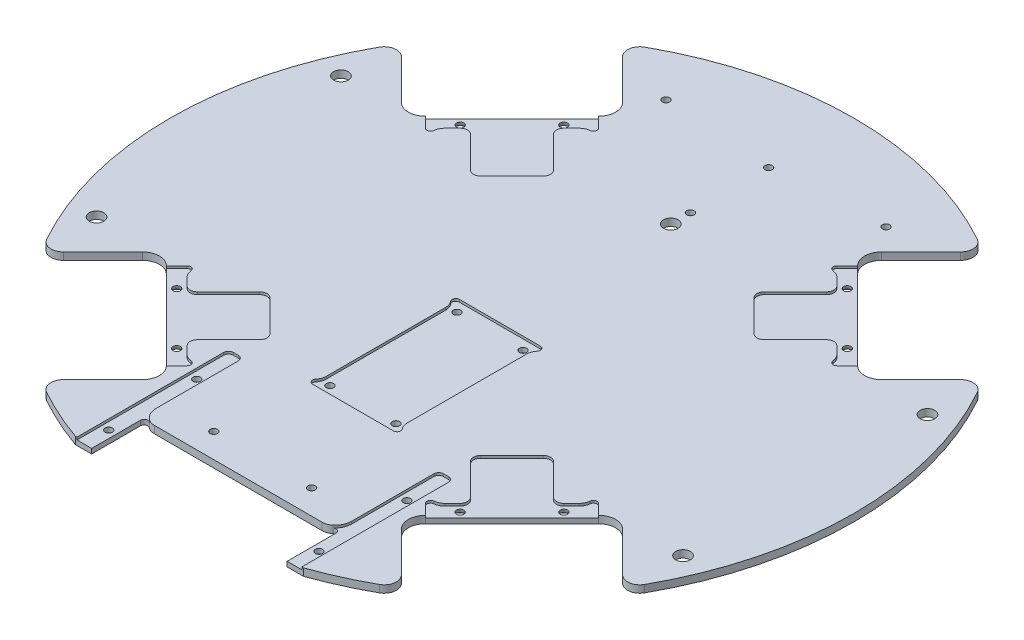
SolidWorks part; units mm, degrees
material "1060 Alloy"
ref_plane "Front Plane" through (0, 0, 0) normal (0, 0, 1) x (1, 0, 0)
ref_plane "Top Plane" through (0, 0, 0) normal (0, 1, 0) x (1, 0, 0)
ref_plane "Right Plane" through (0, 0, 0) normal (1, 0, 0) x (0, 0, -1)
sketch "Sketch1" plane through (0, 0, 0) normal (0, 1, 0) x (1, 0, 0)
  circle A0 centre (0, 0) radius 140
  dimension "D1" = 280
extrude "Boss-Extrude1" add sketch "Sketch1" along normal blind 3
sketch "Sketch7" plane through (0, 3, 0) normal (0, 1, 0) x (1, 0, 0)
  line L0 (-88.4237, -52.9977) -> (-52.9977, -88.4237)
  line L1 (-98.2525, -52.9977) -> (-121.6224, -76.3675)
  line L2 (-52.9977, -98.2525) -> (-76.3675, -121.6224)
  line L3 (-121.6224, -76.3675) -> (-76.3675, -121.6224)
  line L4 (0, 0) -> (-98.9949, -98.9949) construction
  line L7 (0, 0) -> (0, 130) construction
  circle A0 centre (0, 0) radius 140 construction
  arc A1 (-98.2525, -52.9977) -> (-88.4237, -52.9977) centre (-93.3381, -57.912) cw
  arc A2 (-52.9977, -88.4237) -> (-52.9977, -98.2525) centre (-57.912, -93.3381) cw
  dimension "D4" = 6.95
  dimension "D1" = 100
  dimension "D2" = 64
  dimension "D3" = 135
extrude "Cut-Extrude4" cut sketch "Sketch7" against normal up to next
sketch "Sketch8" plane through (0, 3, 0) normal (0, 1, 0) x (1, 0, 0)
  line L0 (-88.4237, -52.9977) -> (-52.9977, -88.4237)
  line L1 (-88.4237, -52.9977) -> (-84.1811, -48.755)
  line L2 (-52.9977, -88.4237) -> (-48.755, -84.1811)
  line L3 (-80.1836, -52.7525) -> (-52.7525, -80.1836)
  line L6 (-52.9977, -88.4237) -> (-88.4237, -52.9977) construction
  arc A0 (-84.1811, -48.755) -> (-81.6268, -49.6775) centre (-83.1204, -49.8157) cw
  arc A1 (-81.6268, -49.6775) -> (-80.1836, -52.7525) centre (-76.648, -49.217) ccw
  arc A2 (-48.755, -84.1811) -> (-49.6775, -81.6268) centre (-49.8157, -83.1204) ccw
  arc A3 (-49.6775, -81.6268) -> (-52.7525, -80.1836) centre (-49.217, -76.648) cw
  dimension "D2" = 1.5
  dimension "D3" = 5
  dimension "D4" = 1.5
  dimension "D5" = 5
  dimension "D1" = 6
extrude "Cut-Extrude5" cut sketch "Sketch8" against normal blind 1
sketch "Sketch14" plane through (0, 3, 0) normal (0, 1, 0) x (1, 0, 0)
  line L0 (-52.7525, -80.1836) -> (-80.1836, -52.7525) construction
  line L1 (-52.7525, -80.1836) -> (-80.1836, -52.7525) construction
  line L2 (-72.832, -55.8614) -> (-60.1041, -43.1335)
  line L3 (-55.8614, -72.832) -> (-43.1335, -60.1041)
  line L4 (-55.8614, -43.1335) -> (-43.1335, -55.8614)
  line L5 (-77.0746, -55.8614) -> (-55.8614, -77.0746)
  line L8 (-84.1811, -48.755) -> (-88.4237, -52.9977) construction
  arc A0 (-77.0746, -55.8614) -> (-72.832, -55.8614) centre (-74.9533, -53.7401) ccw
  arc A1 (-55.8614, -77.0746) -> (-55.8614, -72.832) centre (-53.7401, -74.9533) cw
  arc A2 (-60.1041, -43.1335) -> (-55.8614, -43.1335) centre (-57.9828, -45.2548) cw
  arc A3 (-43.1335, -60.1041) -> (-43.1335, -55.8614) centre (-45.2548, -57.9828) ccw
  dimension "D1" = 3
  dimension "D2" = 24
  dimension "D3" = 24
  dimension "D4" = 13.05
extrude "Cut-Extrude10" cut sketch "Sketch14" against normal up to surface (1 mm away) up to face at (-67.2361, 2, 67.2361)
sketch "Sketch9" plane through (0, 2, 0) normal (0, 1, 0) x (1, 0, 0)
  line L0 (-48.755, -84.1811) -> (-84.1811, -48.755) construction
  line L3 (-48.755, -84.1811) -> (-84.1811, -48.755) construction
  line L4 (-98.2525, -52.9977) -> (-119.0017, -73.7469) construction
  circle A0 centre (-79.196, -57.9828) radius 1.5
  circle A1 centre (-57.9828, -79.196) radius 1.5
  dimension "D4" = 3
  dimension "D1" = 3
  dimension "D2" = 30
  dimension "D3" = 17
  dimension "D5" = 3
extrude "Cut-Extrude6" cut sketch "Sketch9" against normal up to next
fillet "Fillet1" radius 5 2 edges at (-73.7469, 1.5, 119.0017) (-119.0017, 1.5, 73.7469)
pattern_circular "CirPattern1" count 4 over 360 about axis through (0, 3, 0) along (0, 1, 0) of "Cut-Extrude4", "Cut-Extrude6", "Fillet1", "Cut-Extrude5", "Cut-Extrude10"
sketch "Sketch2" plane through (0, 3, 0) normal (0, 1, 0) x (1, 0, 0)
  line L0 (-46.6476, -132) -> (-40, -132)
  line L1 (-40, -132) -> (-40, -112)
  line L2 (-34.3467, -112) -> (34.3467, -112)
  line L3 (40, -112) -> (40, -132)
  line L4 (40, -132) -> (46.6476, -132)
  line L5 (46.6476, -132) -> (46.6476, -140)
  line L6 (46.6476, -140) -> (-46.6476, -140)
  line L7 (-46.6476, -140) -> (-46.6476, -132)
  circle A0 centre (0, 0) radius 140 construction
  arc A1 (-40, -112) -> (-37.5415, -110.8462) centre (-38.5, -112) cw
  arc A2 (-34.3467, -112) -> (-37.5415, -110.8462) centre (-34.3467, -107) cw
  arc A3 (40, -112) -> (37.5415, -110.8462) centre (38.5, -112) ccw
  arc A4 (34.3467, -112) -> (37.5415, -110.8462) centre (34.3467, -107) ccw
  dimension "D5" = 1.5
  dimension "D6" = 5
  dimension "D1" = 8
  dimension "D2" = 20
  dimension "D3" = 80
  dimension "D4" = 6.6476
extrude "Cut-Extrude1" cut sketch "Sketch2" against normal up to next
sketch "Sketch3" plane through (0, 3, 0) normal (0, 1, 0) x (1, 0, 0)
  line L0 (-40, -132) -> (-46.6476, -132) construction
  line L1 (-40, -132) -> (-46, -132)
  line L2 (-40, -132) -> (-40, -72)
  line L3 (-42, -70) -> (-44, -70)
  line L4 (-46, -132) -> (-46, -72)
  line L5 (40, -132) -> (46, -132)
  line L6 (40, -132) -> (40, -72)
  line L7 (42, -70) -> (44, -70)
  line L8 (46, -132) -> (46, -72)
  line L12 (-40, -112) -> (-40, -132) construction
  line L13 (40, -132) -> (40, -112) construction
  arc A0 (40, -72) -> (42, -70) centre (42, -72) cw
  arc A1 (44, -70) -> (46, -72) centre (44, -72) cw
  arc A2 (-40, -72) -> (-42, -70) centre (-42, -72) ccw
  arc A3 (-44, -70) -> (-46, -72) centre (-44, -72) ccw
  dimension "D5" = 2
  dimension "D1" = 6
  dimension "D2" = 62
extrude "Cut-Extrude2" cut sketch "Sketch3" against normal blind 1
sketch "Sketch18" plane through (0, 3, 0) normal (0, 1, 0) x (1, 0, 0)
  line L0 (-40, -112) -> (-40, -72) construction
  line L1 (-40, -112) -> (-40, -72) construction
  line L3 (-40, -105.608) -> (-40, -112)
  line L4 (-40, -112) -> (-37.5415, -110.8462)
  line L5 (40, -72) -> (40, -112) construction
  line L6 (40, -105.608) -> (40, -112)
  line L7 (40, -112) -> (37.5415, -110.8462)
  arc A0 (-37.5415, -110.8462) -> (-40, -105.608) centre (-33.1904, -105.608) cw
  arc A2 (-37.5415, -110.8462) -> (-34.3467, -112) centre (-34.3467, -107) ccw construction
  arc A3 (37.5415, -110.8462) -> (40, -105.608) centre (33.1904, -105.608) ccw
  arc A4 (34.3467, -112) -> (37.5415, -110.8462) centre (34.3467, -107) ccw construction
extrude "Cut-Extrude14" cut sketch "Sketch18" against normal up to surface (1 mm away) up to face at (42.5714, 2, 94.1674)
fillet "Fillet3" radius 1.5 8 edges at (57.9828, 0, 80.696) (79.196, 0, 59.4828) (79.196, 0, -56.4828) (57.9828, 0, -77.696) (-57.9828, 0, -77.696) (-79.196, 0, -56.4828) (-57.9828, 0, 80.696) (-79.196, 0, 59.4828)
sketch "Sketch10" plane through (0, 3, 0) normal (0, 1, 0) x (1, 0, 0)
  circle A0 centre (-13.5, -61) radius 1.5
  circle A1 centre (13.5, -61) radius 1.5
  circle A2 centre (-13.5, -9) radius 1.5
  circle A3 centre (13.5, -9) radius 1.5
  dimension "D3" = 3
  dimension "D1" = 13.5
  dimension "D2" = 27
  dimension "D4" = 61
  dimension "D5" = 52
extrude "Cut-Extrude7" cut sketch "Sketch10" against normal up to next
sketch "Sketch11" plane through (0, 3, 0) normal (0, 1, 0) x (1, 0, 0)
  line L0 (34.3467, -112) -> (-34.3467, -112) construction
  circle A0 centre (-20, -102) radius 1.5
  circle A1 centre (20, -102) radius 1.5
  dimension "D1" = 3
  dimension "D2" = 40
  dimension "D3" = 10
  dimension "D4" = 20
extrude "Cut-Extrude8" cut sketch "Sketch11" against normal up to next
sketch "Sketch13" plane through (0, 3, 0) normal (0, 1, 0) x (1, 0, 0)
  line L0 (-46, -132) -> (-40, -132) construction
  line L4 (-40, -105.608) -> (-40, -72) construction
  line L5 (40, -72) -> (40, -105.608) construction
  circle A0 centre (-43, -86) radius 1.5
  circle A1 centre (-43, -122) radius 1.5
  circle A2 centre (43, -122) radius 1.5
  circle A3 centre (43, -86) radius 1.5
  dimension "D1" = 3
  dimension "D2" = 10
  dimension "D3" = 36
  dimension "D4" = 3
  dimension "D5" = 3
extrude "Cut-Extrude9" cut sketch "Sketch13" against normal up to next
sketch "Sketch15" plane through (0, 3, 0) normal (0, 1, 0) x (1, 0, 0)
  line L1 (-16.55, -4.95) -> (16.55, -4.95)
  line L2 (-16.55, -10.6033) -> (-16.55, -59.3967)
  line L3 (-16.55, -65.05) -> (16.55, -65.05)
  line L4 (16.55, -10.6033) -> (16.55, -59.3967)
  circle A0 centre (-13.5, -61) radius 1.5 construction
  circle A1 centre (-13.5, -9) radius 1.5 construction
  arc A2 (-16.55, -4.95) -> (-17.7038, -7.4085) centre (-16.55, -6.45) ccw
  arc A3 (-16.55, -10.6033) -> (-17.7038, -7.4085) centre (-21.55, -10.6033) ccw
  arc A4 (16.55, -4.95) -> (17.7038, -7.4085) centre (16.55, -6.45) cw
  arc A5 (17.7038, -7.4085) -> (16.55, -10.6033) centre (21.55, -10.6033) ccw
  arc A6 (-16.55, -65.05) -> (-17.7038, -62.5915) centre (-16.55, -63.55) cw
  arc A7 (-17.7038, -62.5915) -> (-16.55, -59.3967) centre (-21.55, -59.3967) ccw
  arc A8 (16.55, -65.05) -> (17.7038, -62.5915) centre (16.55, -63.55) ccw
  arc A9 (17.7038, -62.5915) -> (16.55, -59.3967) centre (21.55, -59.3967) cw
  dimension "D3" = 4.05
  dimension "D5" = 1.5
  dimension "D6" = 5
  dimension "D1" = 33.1
  dimension "D2" = 4.05
  dimension "D4" = 16.55
extrude "Cut-Extrude11" cut sketch "Sketch15" against normal blind 1
sketch "Sketch16" plane through (0, 3, 0) normal (0, 1, 0) x (1, 0, 0)
  circle A0 centre (0, 73) radius 1.5
  circle A1 centre (-45, 108) radius 1.5
  circle A2 centre (45, 108) radius 1.5
  circle A3 centre (0, 105) radius 1.5
  circle A4 centre (0, 65) radius 3
  dimension "D2" = 3
  dimension "D5" = 6
  dimension "D1" = 73
  dimension "D3" = 108
  dimension "D4" = 90
  dimension "D6" = 32
  dimension "D7" = 65
extrude "Cut-Extrude12" cut sketch "Sketch16" against normal up to next
sketch "Sketch17" plane through (0, 3, 0) normal (0, 1, 0) x (1, 0, 0)
  circle A0 centre (-120, 50) radius 3
  circle A1 centre (-120, -50) radius 3
  circle A2 centre (120, 50) radius 3
  circle A3 centre (120, -50) radius 3
  dimension "D1" = 6
  dimension "D2" = 50
  dimension "D3" = 50
  dimension "D4" = 120
  dimension "D5" = 120
extrude "Cut-Extrude13" cut sketch "Sketch17" against normal up to next
